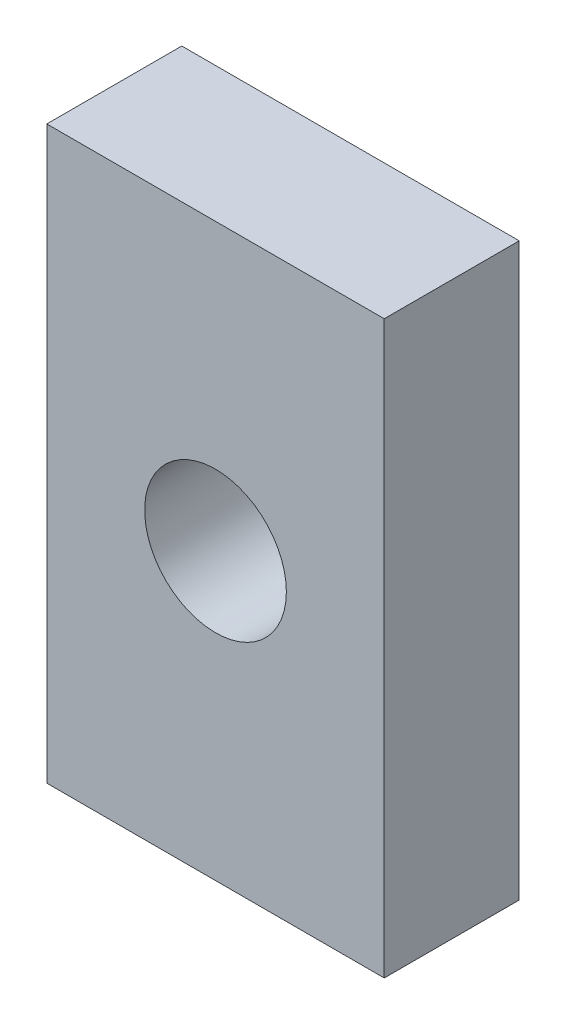
SolidWorks part; units mm, degrees
ref_plane "Front Plane" through (0, 0, 0) normal (0, 0, 1) x (1, 0, 0)
ref_plane "Top Plane" through (0, 0, 0) normal (0, 1, 0) x (1, 0, 0)
ref_plane "Right Plane" through (0, 0, 0) normal (1, 0, 0) x (0, 0, -1)
sketch "Sketch1" plane through (0, 0, 0) normal (0, 0, 1) x (1, 0, 0)
  line L1 (-12.5, -21.15) -> (12.5, -21.15)
  line L2 (-12.5, -21.15) -> (-12.5, 21.15)
  line L3 (-12.5, 21.15) -> (12.5, 21.15)
  line L4 (12.5, -21.15) -> (12.5, 21.15)
  line L5 (-12.5, -21.15) -> (12.5, 21.15) construction
  line L6 (-12.5, 21.15) -> (12.5, -21.15) construction
  circle A0 centre (0, 0) radius 5.25
  point P0 (0, 0)
  dimension "D3" = 10.5
  dimension "D1" = 21.15
extrude "Boss-Extrude1" add sketch "Sketch1" along normal blind 10
